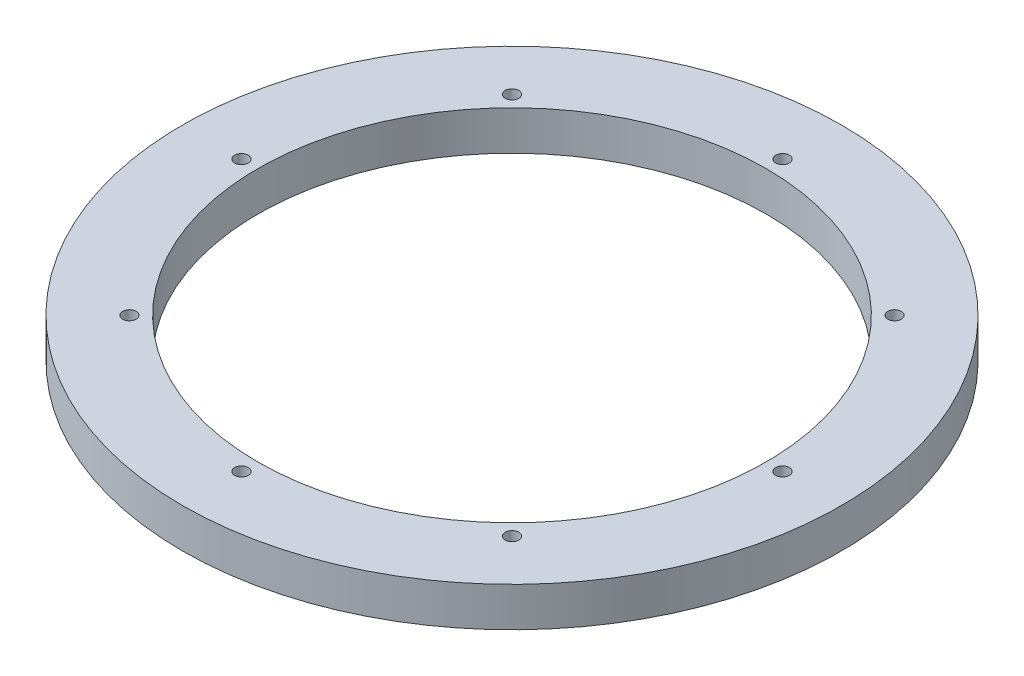
SolidWorks part; units mm, degrees
material "6061 Alloy"
ref_plane "Front Plane" through (0, 0, 0) normal (0, 0, 1) x (1, 0, 0)
ref_plane "Top Plane" through (0, 0, 0) normal (0, 1, 0) x (1, 0, 0)
ref_plane "Right Plane" through (0, 0, 0) normal (1, 0, 0) x (0, 0, -1)
sketch "Sketch1" plane through (0, 0, 0) normal (0, 1, 0) x (1, 0, 0)
  circle A0 centre (0, 0) radius 49.2125
  circle A1 centre (0, 0) radius 63.8175
  circle A2 centre (0, 0) radius 60.6425
  circle A3 centre (0, -52.3875) radius 1.3208
  circle A4 centre (-37.0436, -37.0436) radius 1.3208
  circle A5 centre (-52.3875, 0) radius 1.3208
  circle A6 centre (-37.0436, 37.0436) radius 1.3208
  circle A7 centre (0, 52.3875) radius 1.3208
  circle A8 centre (37.0436, 37.0436) radius 1.3208
  circle A9 centre (52.3875, 0) radius 1.3208
  circle A10 centre (37.0436, -37.0436) radius 1.3208
  point P21 (0, 0)
  dimension "D1" = 98.425
  dimension "D4" = 2.6416
  dimension "D5" = 52.3875
  dimension "D2" = 14.605
  dimension "D3" = 11.43
  dimension "D6" = 8
extrude "Boss-Extrude1" add sketch "Sketch1" along normal blind 7.62 contours A2 A0 | A1 A2 region at (-62.0125, 0, 0) region at (-58.9273, 0, 0)
sketch "Sketch2" plane through (0, 0, 0) normal (1, 0, 0) x (0, 0, -1)
  line L0 (-63.8175, 0) -> (63.8175, 0) construction
  line L1 (63.8175, 7.62) -> (-63.8175, 7.62) construction
  line L2 (-63.8175, 0) -> (63.8175, 0)
  line L3 (63.8175, 7.62) -> (-63.8175, 7.62)
  line L4 (89.5975, 6.858) -> (99.9841, 6.858) construction
  line L5 (95.9885, 5.08) -> (99.6739, 5.08) construction
  line L6 (0, 0) -> (0, 18.217) construction
  circle A0 centre (60.6425, 8.4455) radius 1.5875 construction
  circle A1 centre (60.6425, 8.509) radius 1.651
  circle A2 centre (60.6425, 1.651) radius 1.651
  dimension "D3" = 3.175
  dimension "D4" = 3.302
  dimension "D1" = 60.6425
  dimension "D2" = 0.762
  dimension "D5" = 2.54
equation "\"Middle Coupler Inner Daimeter\"= 3.875in"
equation "\"Middle Coupler  Wall Thickness\" = 0.25in"
equation "\"Middle Coupler Bottom Thickness\"= 0.2in"
equation "\"Bearing Rail Offset\"= 0.45in"
equation "\"3-56 UNF Tap\"= 0.089in"
equation "\"3-56 UNF Clearance\"= 0.104in"
equation "\"D5@Sketch1\"=(\"Middle Coupler Inner Daimeter\"*2+0.5)/4in"
equation "\"Ball Bearing Distance\"= 0.03in"
equation "\"D1@Sketch2\"=\"Middle Coupler Inner Daimeter\"/2+\"Bearing Rail Offset\""
equation "\"D3@Sketch1\"=\"Bearing Rail Offset\""
equation "\"D4@Sketch1\"=\"3-56 UNF Clearance\""
equation "\"D1@Sketch1\"=\"Middle Coupler Inner Daimeter\""
equation "\"D2@Sketch2\"=\"Ball Bearing Distance\""
equation "\"D4@Sketch2\"=\"D3@Sketch2\"+0.005"
equation "\"D5@Sketch2\"=\"Middle Coupler Bottom Thickness\"/2"
equation "\"TCA Outer Diameter\" = 6in"
equation "\"Interstage Aeroframe Wall Thickness\" = 0.072in"
equation "\"Compression Spring OD\"= 0.42in"
equation "\"10-24 Tap\"= 0.157in"
equation "\"10-24 Clearance\"= 0.196in"
equation "\"Lower Stage Fuselage Wall Thickness\" = 0.25in"
equation "\"6-32 Tap\" = 0.107in"
equation "\"1/4-20 Tap\" = 0.201in"
